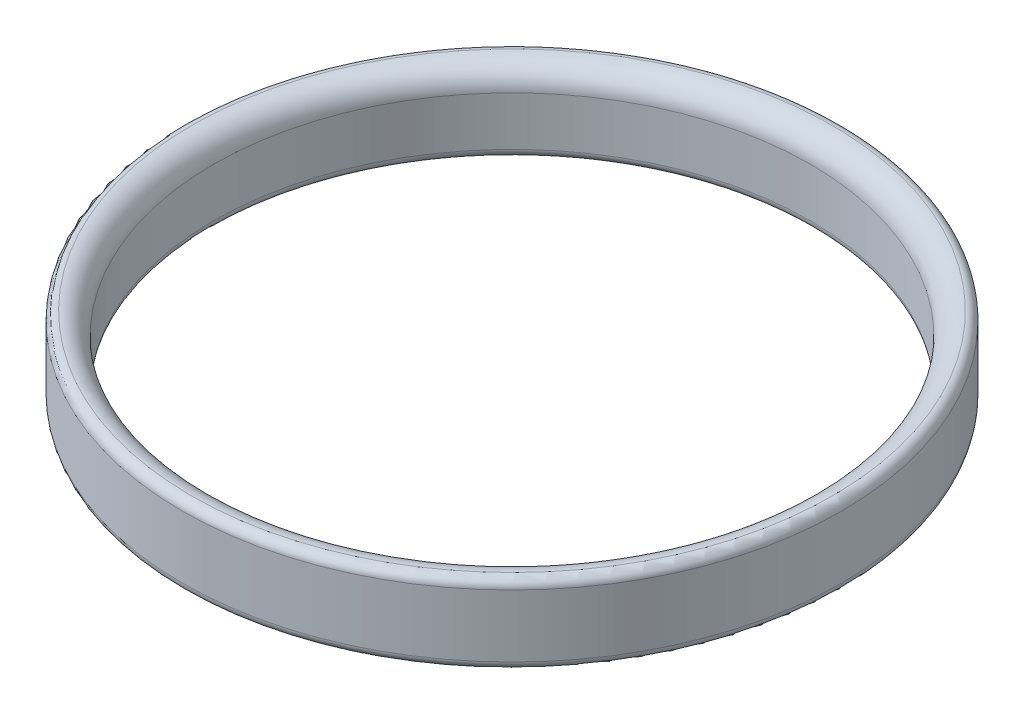
SolidWorks part; units mm, degrees
ref_plane "Front Plane" through (0, 0, 0) normal (0, 0, 1) x (1, 0, 0)
ref_plane "Top Plane" through (0, 0, 0) normal (0, 1, 0) x (1, 0, 0)
ref_plane "Right Plane" through (0, 0, 0) normal (1, 0, 0) x (0, 0, -1)
sketch "Sketch1" plane through (0, 0, 0) normal (0, 1, 0) x (1, 0, 0)
  circle A0 centre (0, 0) radius 6.7
  circle A1 centre (0, 0) radius 7.4
  dimension "D1" = 14.8
  dimension "D2" = 0.7
extrude "Boss-Extrude1" add sketch "Sketch1" along normal blind 1.8
fillet "Fillet1" radius 0.5 1 edges at (0, 1.8, 6.7)
fillet "Fillet2" radius 0.2 3 edges at (0, 0, 7.4) (0, 1.8, 7.4) (0, 0, 6.7)
